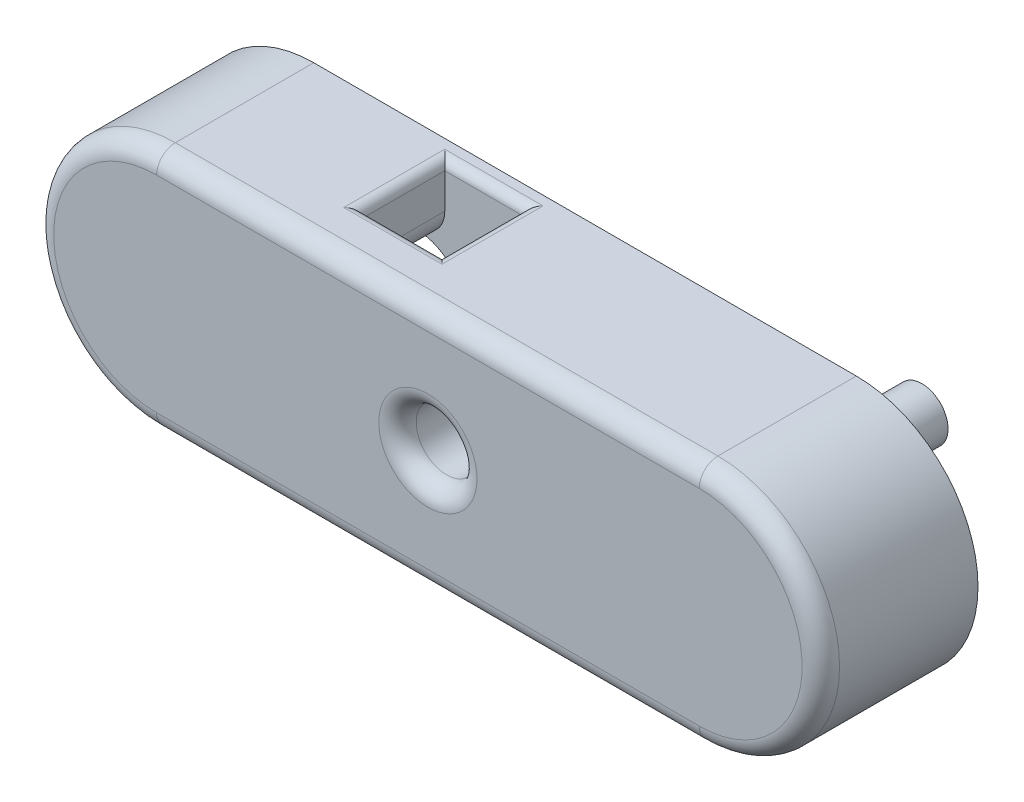
SolidWorks part; units mm, degrees
ref_plane "Front Plane" through (0, 0, 0) normal (0, 0, 1) x (1, 0, 0)
ref_plane "Top Plane" through (0, 0, 0) normal (0, 1, 0) x (1, 0, 0)
ref_plane "Right Plane" through (0, 0, 0) normal (1, 0, 0) x (0, 0, -1)
sketch "Sketch1" plane through (0, 0, 0) normal (0, 0, 1) x (1, 0, 0)
  line L0 (29, 13) -> (-29, 13) construction
  line L1 (-29, -13) -> (29, -13) construction
  line L2 (29, 13) -> (-29, 13)
  line L3 (-29, -13) -> (29, -13)
  arc A0 (-29, 13) -> (-29, -13) centre (-29, 0) ccw construction
  arc A1 (29, -13) -> (29, 13) centre (29, 0) ccw construction
  arc A2 (-29, 13) -> (-29, -13) centre (-29, 0) ccw
  arc A3 (29, -13) -> (29, 13) centre (29, 0) ccw
  circle A9 centre (-35, 0) radius 3 construction
  circle A10 centre (17, 6) radius 3 construction
  circle A11 centre (17, -6) radius 3 construction
  circle A12 centre (29, -6) radius 3 construction
  circle A13 centre (29, 6) radius 3 construction
  circle A14 centre (-35, 0) radius 3
  circle A15 centre (17, 6) radius 3
  circle A16 centre (17, -6) radius 3
  circle A17 centre (29, -6) radius 3
  circle A18 centre (29, 6) radius 3
  circle A19 centre (17, 6) radius 2.8
  circle A20 centre (29, 6) radius 2.8
  circle A21 centre (29, -6) radius 2.8
  circle A22 centre (17, -6) radius 2.8
  circle A23 centre (-35, 0) radius 2.8
  circle A24 centre (-16, 0) radius 5.05 construction
  circle A25 centre (0, 0) radius 5.05 construction
  circle A26 centre (-16, 0) radius 5.05
  circle A27 centre (0, 0) radius 5.05
  dimension "D1" = 0.2
extrude "Boss-Extrude1" add sketch "Sketch1" against normal offset from surface (7 mm away) 0.4 contours A23 | A20 | A21 region at (29, 6, 0) region at (29, -6, 0) region at (-35, 0, 0)
extrude "Boss-Extrude2" add sketch "Sketch1<3>" along normal blind 2 contours L3 A3 L2 A2 A27 A26 A18 A17 A16 A15 A14 | A14 | A16 | A17 | A18 | A15 region at (41.1207, 0, 0)
sketch "Sketch1<3>" plane through (0, 0, 0) normal (0, 0, 1) x (1, 0, 0) same geometry as "Sketch1"
sketch "Sketch5" plane through (0, 0, 2) normal (0, 0, 1) x (1, 0, 0)
  line L0 (-11.8, 13) -> (-11.8, -13) construction
  line L1 (29, 13) -> (-29, 13) construction
  line L2 (-29, -13) -> (29, -13) construction
  line L3 (-4.8, 13) -> (-4.8, -13) construction
  line L4 (-4.5, -13) -> (-4.5, -9.55)
  line L5 (-13, 13) -> (-29, 13)
  line L6 (-29, -13) -> (-13, -13)
  line L7 (0, -5.05) -> (0, 5.05) construction
  line L8 (29, -13) -> (-4.5, -13)
  line L9 (-4.5, 13) -> (29, 13)
  line L10 (-4.5, 13) -> (-4.5, 9.55)
  line L11 (-13, 13) -> (-13, 8.25)
  line L12 (-13, -13) -> (-13, -8.25)
  line L13 (-16, -5.25) -> (-16, 5.25) construction
  circle A2 centre (-16, 0) radius 5.05 construction
  circle A3 centre (-16, 0) radius 5.05
  circle A4 centre (-16, 0) radius 5.25
  arc A7 (-29, 13) -> (-29, -13) centre (-29, 0) ccw construction
  arc A8 (-29, 13) -> (-29, -13) centre (-29, 0) ccw
  circle A10 centre (0, 0) radius 5.05 construction
  circle A11 centre (0, 0) radius 5.05
  arc A14 (29, -13) -> (29, 13) centre (29, 0) ccw construction
  arc A15 (29, -13) -> (29, 13) centre (29, 0) ccw
  arc A18 (-4.5, -9.55) -> (0, -5.05) centre (0, -9.55) cw
  circle A20 centre (0, 0) radius 5.05 construction
  arc A21 (-4.5, 9.55) -> (0, 5.05) centre (0, 9.55) ccw
  arc A22 (-13, -8.25) -> (-16, -5.25) centre (-16, -8.25) ccw
  arc A23 (-13, 8.25) -> (-16, 5.25) centre (-16, 8.25) cw
  arc A25 (0, -5.05) -> (0, 5.05) centre (0, 0) ccw
  arc A26 (-16, 5.25) -> (-16, -5.25) centre (-16, 0) ccw
  circle M3 centre (0, 0) radius 5.05
  line M5 (-29, -13) -> (29, -13)
  arc M6 (29, -13) -> (29, 13) centre (29, 0) ccw
  line M7 (29, 13) -> (-29, 13)
  arc M8 (-29, 13) -> (-29, -13) centre (-29, 0) ccw
  dimension "D1" = 7
  dimension "D3" = 1.2
  dimension "D4" = 1.2
  dimension "D5" = 0.3
  dimension "D6" = 0.3
  dimension "D2" = 0.2
extrude "Boss-Extrude3" add sketch "Sketch5" along normal offset from surface (8.8 mm away) 0.8 contours M3 M5 M6 M7 | A4 M7 M8 M5 region at (19.0735, 0, 2) region at (-27.5385, 0, 2) offset beyond the face yes
sketch "Sketch6" plane through (0, 0, 10.8) normal (0, 0, 1) x (1, 0, 0)
  line L0 (29, 13) -> (-29, 13) construction
  line L1 (-29, -13) -> (29, -13) construction
  line L2 (29, 13) -> (-29, 13)
  line L3 (-29, -13) -> (29, -13)
  arc A0 (29, -13) -> (29, 13) centre (29, 0) ccw construction
  arc A1 (-29, 13) -> (-29, -13) centre (-29, 0) ccw construction
  arc A2 (29, -13) -> (29, 13) centre (29, 0) ccw
  arc A3 (-29, 13) -> (-29, -13) centre (-29, 0) ccw
  circle A4 centre (-16, 0) radius 5.05 construction
  circle A5 centre (-16, 0) radius 5.05
  circle A6 centre (0, 0) radius 3 construction
  circle A7 centre (0, 0) radius 3
  circle A8 centre (0, 0) radius 3.25
  arc M7 (-16, 5.25) -> (-13, 8.25) centre (-16, 8.25) ccw
  line M8 (-13, 8.25) -> (-13, 13)
  line M9 (-13, 13) -> (-29, 13)
  arc M10 (-29, 13) -> (-29, -13) centre (-29, 0) ccw
  line M11 (-29, -13) -> (-13, -13)
  line M12 (-13, -13) -> (-13, -8.25)
  arc M13 (-13, -8.25) -> (-16, -5.25) centre (-16, -8.25) ccw
  arc M14 (-16, -5.25) -> (-16, 5.25) centre (-16, 0) cw
  dimension "D1" = 0.25
extrude "Boss-Extrude4" add sketch "Sketch6" along normal blind 6 contours M14 M7 M8 M9 M10 M11 M12 M13 | L3 A2 L2 A8 A5 M8 M7 M14 M13 M12 | A5 region at (13.5183, 0, 10.8) region at (-27.5385, 0, 10.8) region at (-16, 0, 10.8)
extrude "Cut-Extrude1" cut sketch "Sketch6<4>" along normal offset from surface (4 mm away) 2 contours A5 up to face at (0, 0, 16.8)
sketch "Sketch6<4>" plane through (0, 0, 10.8) normal (0, 0, 1) x (1, 0, 0) same geometry as "Sketch6"
fillet "Fillet1" radius 2 5 edges at (3.25, 0, 16.8) (0, -13, 16.8) (-42, 0, 16.8) (0, 13, 16.8) (42, 0, 16.8)
fillet "Fillet2" radius 1 8 edges at (-8.75, 13, 2) (-13, 13, 6.4) (-8.75, 13, 10.8) (-4.5, 13, 6.4) (-13, -13, 6.4) (-8.75, -13, 2) (-4.5, -13, 6.4) (-8.75, -13, 10.8)
equation "\"D4@Sketch5\"=\"D3@Sketch5\""
equation "\"D5@Sketch5\"=\"D6@Sketch5\""
